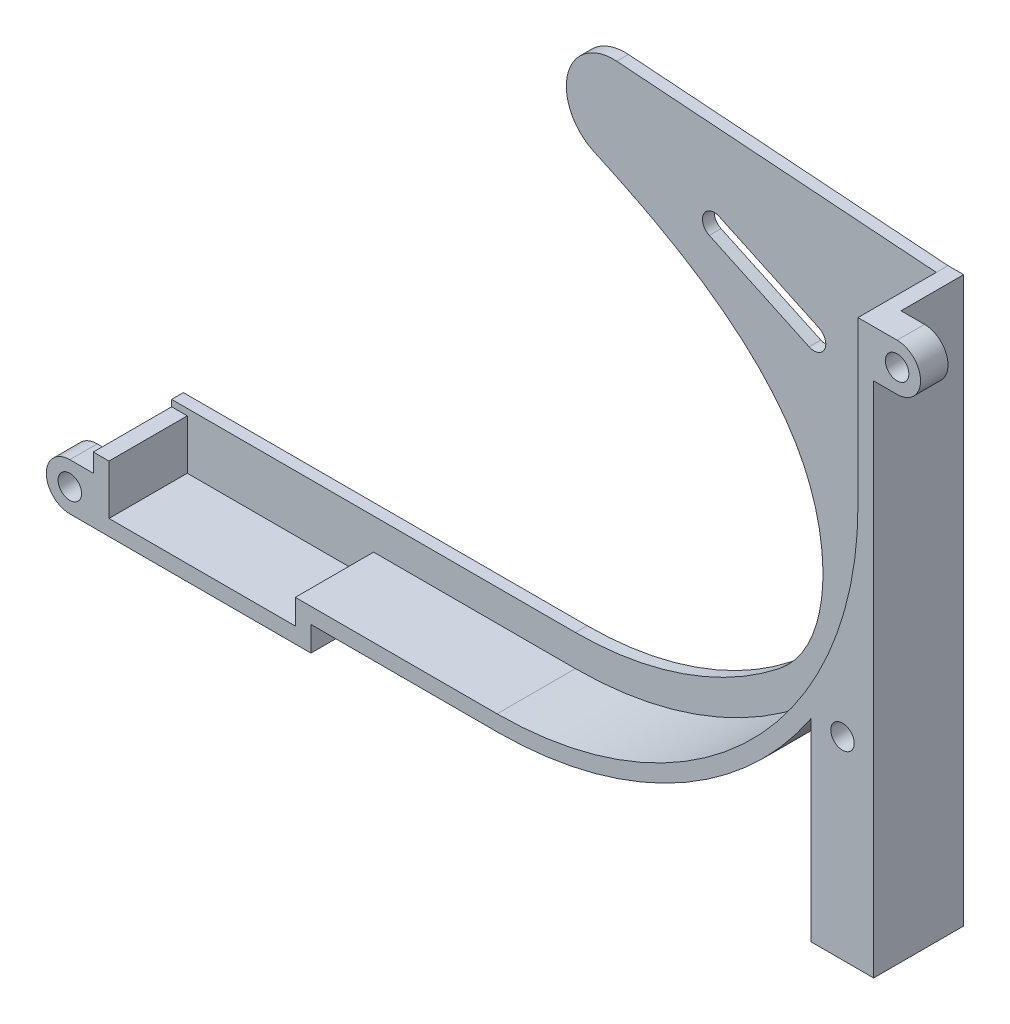
SolidWorks part; units mm, degrees
ref_plane "Front Plane" through (0, 0, 0) normal (0, 0, 1) x (1, 0, 0)
ref_plane "Top Plane" through (0, 0, 0) normal (0, 1, 0) x (1, 0, 0)
ref_plane "Right Plane" through (0, 0, 0) normal (1, 0, 0) x (0, 0, -1)
sketch "Sketch1" plane through (0, 0, 0) normal (0, 0, 1) x (1, 0, 0)
  line L0 (-18.1262, 8.4524) -> (18.1262, -8.4524) construction
  line L1 (0, 0) -> (25.201, 0) construction
  line L2 (23.1262, 11.4863) -> (23.1262, -9.2963)
  line L3 (-22.9677, -55.3901) -> (-48.7407, -55.3901)
  line L4 (-48.7407, -55.3901) -> (-48.7407, -58.5651)
  line L5 (-48.7407, -58.5651) -> (-72.5407, -58.5651)
  line L6 (-72.5407, -58.5651) -> (-72.5407, -52.2151)
  line L7 (25.1262, 11.4863) -> (25.1262, -9.2963)
  line L8 (-22.9677, -57.3901) -> (-46.7407, -57.3901)
  line L9 (-46.7407, -57.3901) -> (-46.7407, -60.5651)
  line L10 (-46.7407, -60.5651) -> (-74.5407, -60.5651)
  line L11 (-74.5407, -60.5651) -> (-74.5407, -52.2151)
  line L12 (-72.5407, -52.2151) -> (-74.5407, -52.2151)
  line L13 (23.1262, 11.4863) -> (25.1262, 11.4863)
  arc A0 (23.1262, -9.2963) -> (-22.9677, -55.3901) centre (-22.9677, -9.2963) cw
  arc A1 (25.1262, -9.2963) -> (-22.9677, -57.3901) centre (-22.9677, -9.2963) cw
  point P3 (0, 0)
  dimension "D1" = 40
  dimension "D2" = 25
  dimension "D3" = 5
  dimension "D4" = 23.8
  dimension "D5" = 3.175
  dimension "D6" = 6.35
  dimension "D7" = 2
extrude "Boss-Extrude1" add sketch "Sketch1" along normal blind 10
sketch "Sketch2" plane through (0, 0, 0) normal (0, 0, -1) x (-1, 0, 0)
  line L1 (-23.1262, 11.4863) -> (17.6936, 14.4368)
  line L4 (18.1262, 8.4524) -> (-18.1262, -8.4524) construction
  line L5 (-7.5168, -3.5051) -> (5.2321, 2.4397) construction
  line L6 (-8.1507, -2.1457) -> (4.5981, 3.7992)
  line L7 (-6.8829, -4.8646) -> (5.866, 1.0803)
  line L11 (52.7407, -51.3901) -> (74.5407, -51.3901)
  line L38 (74.5407, -51.3901) -> (74.5407, -52.2151)
  line L39 (-25.1262, 11.4863) -> (-23.1262, 11.4863)
  line L48 (-19.1262, -9.2963) -> (-19.1262, 15.4863)
  line L49 (-19.1262, 15.4863) -> (-29.1262, 15.4863)
  line L50 (-29.1262, 15.4863) -> (-29.1262, -9.2963)
  line L51 (22.9677, -61.3901) -> (42.7407, -61.3901)
  line L52 (42.7407, -61.3901) -> (42.7407, -64.5651)
  line L53 (42.7407, -64.5651) -> (78.5407, -64.5651)
  line L54 (78.5407, -64.5651) -> (78.5407, -48.2151)
  line L55 (78.5407, -48.2151) -> (68.5407, -48.2151)
  line L56 (68.5407, -48.2151) -> (68.5407, -54.5651)
  line L57 (68.5407, -54.5651) -> (52.7407, -54.5651)
  line L58 (52.7407, -54.5651) -> (52.7407, -51.3901)
  line L59 (52.7407, -51.3901) -> (22.9677, -51.3901)
  line L71 (52.7407, -51.3901) -> (22.9677, -51.3901)
  line L74 (-23.1262, 11.4863) -> (-25.1262, 11.4863)
  line L75 (-25.1262, 11.4863) -> (-25.1262, -9.2963)
  line L76 (22.9677, -57.3901) -> (46.7407, -57.3901)
  line L77 (46.7407, -57.3901) -> (46.7407, -60.5651)
  line L78 (46.7407, -60.5651) -> (74.5407, -60.5651)
  line L79 (74.5407, -60.5651) -> (74.5407, -52.2151)
  line L80 (74.5407, -52.2151) -> (72.5407, -52.2151)
  line L81 (72.5407, -52.2151) -> (72.5407, -58.5651)
  line L82 (72.5407, -58.5651) -> (48.7407, -58.5651)
  line L83 (48.7407, -58.5651) -> (48.7407, -55.3901)
  line L84 (48.7407, -55.3901) -> (22.9677, -55.3901)
  line L85 (-23.1262, -9.2963) -> (-23.1262, 11.4863)
  line L87 (-25.1262, 11.4863) -> (-25.1262, -9.2963)
  line L88 (22.9677, -57.3901) -> (46.7407, -57.3901)
  line L89 (46.7407, -57.3901) -> (46.7407, -60.5651)
  line L90 (46.7407, -60.5651) -> (74.5407, -60.5651)
  line L91 (74.5407, -60.5651) -> (74.5407, -52.2151)
  arc A1 (20.6619, 3.0145) -> (17.6936, 14.4368) centre (18.1262, 8.4524) ccw
  arc A6 (-8.1507, -2.1457) -> (-6.8829, -4.8646) centre (-7.5168, -3.5051) ccw
  arc A7 (5.866, 1.0803) -> (4.5981, 3.7992) centre (5.2321, 2.4397) ccw
  arc A8 (-29.1262, -9.2963) -> (22.9677, -61.3901) centre (22.9677, -9.2963) ccw
  arc A9 (-19.1262, -9.2963) -> (22.9677, -51.3901) centre (22.9677, -9.2963) ccw
  arc A11 (-3.1097, -42.3396) -> (22.9677, -51.3901) centre (22.9677, -9.2963) ccw
  arc A12 (-25.1262, -9.2963) -> (22.9677, -57.3901) centre (22.9677, -9.2963) ccw
  arc A13 (-23.1262, -9.2963) -> (22.9677, -55.3901) centre (22.9677, -9.2963) ccw
  arc A14 (-25.1262, -9.2963) -> (22.9677, -57.3901) centre (22.9677, -9.2963) ccw
  spline S0 degree 3 poles (20.6619, 3.0145) (14.467, 0.1258) (-11.1415, -11.2332) (-9.493, -37.302) (-3.1097, -42.3396) knots 0 0 0 0 0.582936 1 1 1 1
  point P20 (-1.1424, -0.5327)
  dimension "D3" = 1.5
  dimension "D4" = 6
  dimension "D1" = 4
  dimension "D2" = 0
extrude "Boss-Extrude2" add sketch "Sketch2" along normal blind 1.5
sketch "Sketch4" plane through (0, 0, -1.5) normal (0, 0, -1) x (-1, 0, 0)
  line L0 (-25.1262, -9.2963) -> (-25.1262, -60.5651)
  line L1 (-25.1262, -60.5651) -> (-17.1262, -60.5651)
  line L2 (-17.1262, -60.5651) -> (-17.1262, -35.8576)
  line L3 (46.7407, -60.5651) -> (74.5407, -60.5651) construction
  line L4 (-28.1262, 11.4863) -> (-25.1262, 11.4863)
  line L5 (-28.1262, 5.4863) -> (-25.1262, 5.4863)
  line L6 (-25.1262, 11.4863) -> (-25.1262, -9.2963) construction
  line L7 (-25.1262, 11.4863) -> (-25.1262, 5.4863)
  line L8 (74.5407, -60.5651) -> (74.5407, -51.3901) construction
  line L9 (74.5407, -60.5651) -> (74.5407, -54.5651)
  line L10 (74.5407, -60.5651) -> (77.5407, -60.5651)
  line L11 (77.5407, -54.5651) -> (74.5407, -54.5651)
  arc A0 (-25.1262, -9.2963) -> (22.9677, -57.3901) centre (22.9677, -9.2963) ccw construction
  arc A3 (-28.1262, 11.4863) -> (-28.1262, 5.4863) centre (-28.1262, 8.4863) ccw
  arc A4 (77.5407, -60.5651) -> (77.5407, -54.5651) centre (77.5407, -57.5651) ccw
  arc A5 (-25.1262, -9.2963) -> (22.9677, -57.3901) centre (22.9677, -9.2963) ccw construction
  arc A6 (-25.1262, -9.2963) -> (-17.1262, -35.8576) centre (22.9677, -9.2963) ccw
  circle A7 centre (-28.1262, 8.4863) radius 1.5
  circle A8 centre (77.5407, -57.5651) radius 1.5
  circle A9 centre (-21.1479, -35.8576) radius 1.5
  dimension "D2" = 3
  dimension "D3" = 6
  dimension "D4" = 3
  dimension "D5" = 3
  dimension "D1" = 8
extrude "Boss-Extrude3" add sketch "Sketch4" against normal up to surface (11.5 mm away) up to face at (-29.6464, -41.6699, 10)
sketch "Sketch5" plane through (0, 0, -1.5) normal (0, 0, -1) x (-1, 0, 0)
  line L0 (-25.1262, 5.4863) -> (-25.1262, 11.4863)
  line L1 (74.5407, -54.5651) -> (74.5407, -60.5651)
  line L12 (-23.1262, 11.4863) -> (-28.1262, 11.4863)
  line L13 (-28.1262, 5.4863) -> (-25.1262, 5.4863)
  line L14 (-25.1262, 5.4863) -> (-25.1262, -60.5651)
  line L15 (-25.1262, -60.5651) -> (-17.1262, -60.5651)
  line L16 (-17.1262, -60.5651) -> (-17.1262, -35.8576)
  line L17 (22.9677, -57.3901) -> (46.7407, -57.3901)
  line L18 (46.7407, -57.3901) -> (46.7407, -60.5651)
  line L19 (46.7407, -60.5651) -> (77.5407, -60.5651)
  line L20 (77.5407, -54.5651) -> (74.5407, -54.5651)
  line L21 (74.5407, -54.5651) -> (74.5407, -51.3901)
  line L22 (74.5407, -51.3901) -> (22.9677, -51.3901)
  line L23 (17.6936, 14.4368) -> (-23.1262, 11.4863)
  line L24 (-25.1262, 11.4863) -> (-28.1262, 11.4863)
  line L25 (-28.1262, 5.4863) -> (-25.1262, 5.4863)
  line L31 (74.5407, -60.5651) -> (77.5407, -60.5651)
  line L32 (77.5407, -54.5651) -> (74.5407, -54.5651)
  arc A1 (77.5407, -60.5651) -> (77.5407, -54.5651) centre (77.5407, -57.5651) ccw
  arc A2 (77.5407, -60.5651) -> (77.5407, -54.5651) centre (77.5407, -57.5651) ccw construction
  circle A3 centre (-21.1479, -35.8576) radius 3
  arc A9 (-28.1262, 11.4863) -> (-28.1262, 5.4863) centre (-28.1262, 8.4863) ccw
  arc A10 (-17.1262, -35.8576) -> (22.9677, -57.3901) centre (22.9677, -9.2963) ccw
  arc A11 (77.5407, -60.5651) -> (77.5407, -54.5651) centre (77.5407, -57.5651) ccw
  arc A12 (-3.1097, -42.3396) -> (22.9677, -51.3901) centre (22.9677, -9.2963) ccw
  arc A13 (20.6619, 3.0145) -> (17.6936, 14.4368) centre (18.1262, 8.4524) ccw
  arc A14 (-28.1262, 11.4863) -> (-28.1262, 5.4863) centre (-28.1262, 8.4863) ccw
  arc A16 (77.5407, -60.5651) -> (77.5407, -54.5651) centre (77.5407, -57.5651) ccw
  spline S1 degree 3 poles (457.0873, 845.4694) (81.3885, -175.3064) (-156.9601, 73.8373) (229.1068, -13.9969) (-977.9948, -48.7502) knots -1.766509 -1.766509 -1.766509 -1.766509 0.417064 3.019761 3.019761 3.019761 3.019761 only from (-3.1097, -42.3396) to (20.6619, 3.0145)
  line M3 (-23.1262, 11.4863) -> (-28.1262, 11.4863)
  arc M4 (-28.1262, 11.4863) -> (-28.1262, 5.4863) centre (-28.1262, 8.4863) ccw
  line M5 (-28.1262, 5.4863) -> (-25.1262, 5.4863)
  line M12 (46.7407, -60.5651) -> (77.5407, -60.5651)
  arc M13 (77.5407, -60.5651) -> (77.5407, -54.5651) centre (77.5407, -57.5651) ccw
  line M14 (77.5407, -54.5651) -> (74.5407, -54.5651)
  circle M25 centre (-21.1479, -35.8576) radius 1.5
  circle M26 centre (-28.1262, 8.4863) radius 1.5
  circle M27 centre (77.5407, -57.5651) radius 1.5
  dimension "D1" = 6
  dimension "D2" = 0
extrude "Cut-Extrude1" cut sketch "Sketch5" against normal blind 8 contours L1 M14 M12 M13 M27 | A3 M25 | L0 M5 M3 M4 M26 region at (26.6262, 5.5712, -1.5) region at (-74.6255, -57.5651, -1.5) region at (24.0631, -35.8576, -1.5)
